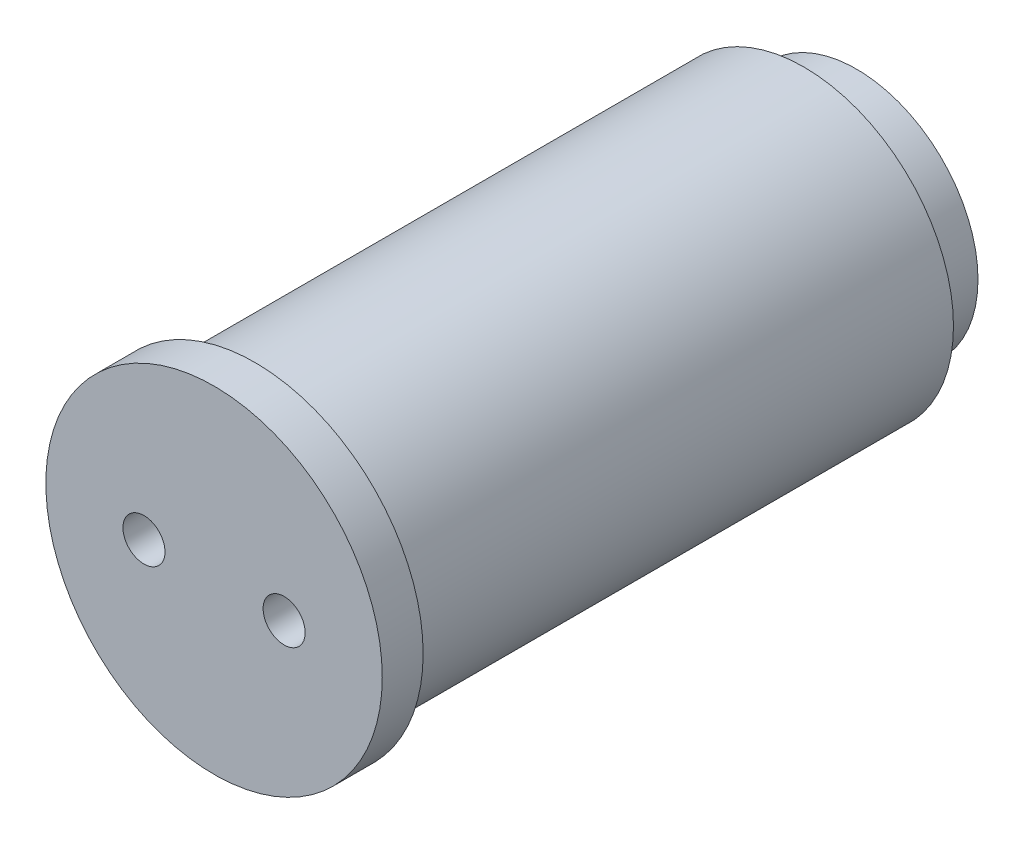
SolidWorks part; units mm, degrees
ref_plane "前视基准面" through (0, 0, 0) normal (0, 0, 1) x (1, 0, 0)
ref_plane "上视基准面" through (0, 0, 0) normal (0, 1, 0) x (1, 0, 0)
ref_plane "右视基准面" through (0, 0, 0) normal (1, 0, 0) x (0, 0, -1)
sketch "草图1" plane through (0, 0, 0) normal (0, 0, 1) x (1, 0, 0)
  circle A0 centre (0, 0) radius 5.2
extrude "凸台-拉伸1" add sketch "草图1" along normal blind 27.5
ref_plane "基准面4" through (0, 0, 13.75) normal (0, 0, 1) x (1, 0, 0)
sketch "草图3" plane through (0, 0, 27.5) normal (0, 0, 1) x (1, 0, 0)
  line L0 (0, 0) -> (0, 5.6384) construction
  circle A0 centre (-3, 0) radius 0.85
  circle A1 centre (3, 0) radius 0.85
  point P9 (0, 0)
  dimension "D1" = 1.7
  dimension "D2" = 3
  dimension "D3" = 2
sketch "草图6" plane through (0, 0, 27.5) normal (0, 0, 1) x (1, 0, 0)
  circle A0 centre (0, 0) radius 7.2
extrude "凸台-拉伸3" add sketch "草图6" against normal blind 1.75
sketch "草图8" plane through (0, 0, 25.75) normal (0, 0, -1) x (-1, 0, 0)
  circle A1 centre (0, 0) radius 6.4
extrude "凸台-拉伸4" add sketch "草图8" along normal blind 23.5
extrude "切除-拉伸4" cut sketch "草图3" against normal blind 8
mirror "镜向3" about plane through (0, 0, 13.75) normal (0, 0, 1) of "切除-拉伸4"
sketch "草图7" plane through (0, 0, 27.5) normal (0, 0, 1) x (1, 0, 0)
  circle A0 centre (-3, 0) radius 0.9
  circle A1 centre (3, 0) radius 0.9
extrude "切除-拉伸5" cut sketch "草图7" against normal up to surface (8 mm away) up to face at (-2.15, 0, 19.5)
